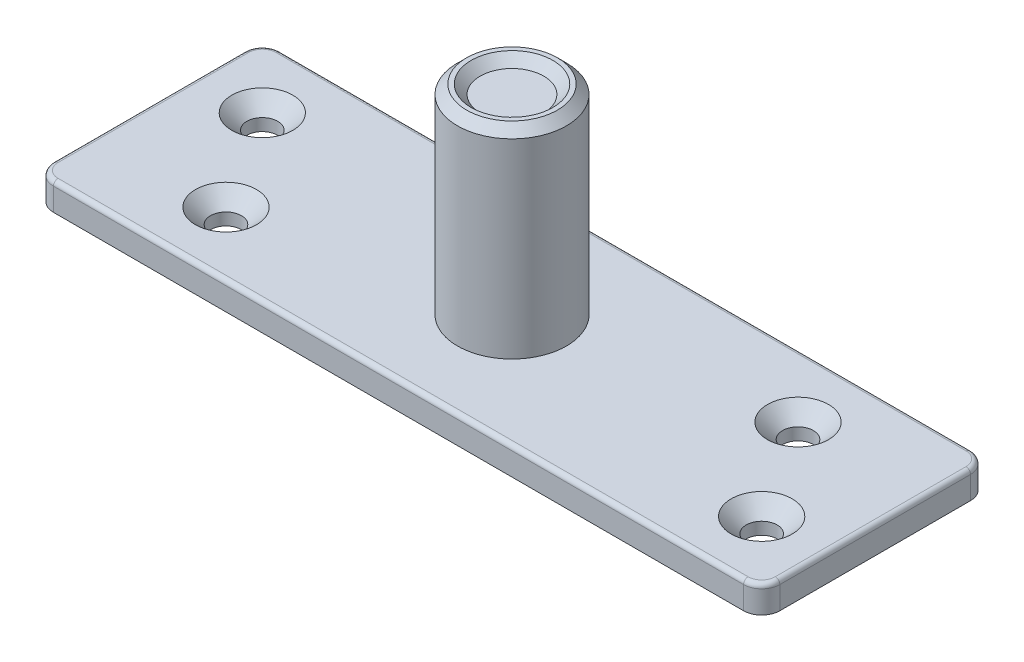
SolidWorks part; units mm, degrees
material "Aço cromo inoxidável"
ref_plane "Plano frontal" through (0, 0, 0) normal (0, 0, 1) x (1, 0, 0)
ref_plane "Plano superior" through (0, 0, 0) normal (0, 1, 0) x (1, 0, 0)
ref_plane "Plano direito" through (0, 0, 0) normal (1, 0, 0) x (0, 0, -1)
other "Caixa delimitadora"
ref_plane "Default Plane" through (-40, -1.5, -12.5) normal (0, 1, 0) x (1, 0, 0)
sketch "Esboço1" plane through (0, 0, 0) normal (0, 1, 0) x (1, 0, 0)
  line L1 (-40, -12.5) -> (40, -12.5)
  line L2 (-40, -12.5) -> (-40, 12.5)
  line L3 (-40, 12.5) -> (40, 12.5)
  line L4 (40, -12.5) -> (40, 12.5)
  line L5 (0, 12.5) -> (0, -12.5) construction
  line L6 (-40, 0) -> (40, 0) construction
  circle A0 centre (0, 0) radius 6
  point P0 (0, 0)
  dimension "D3" = 12
  dimension "D1" = 80
  dimension "D2" = 25
extrude "Ressalto-extrusão1" add sketch "Esboço1" along normal mid plane 3
sketch "Esboço3" plane through (0, -1.5, 0) normal (0, -1, 0) x (1, 0, 0)
  circle A1 centre (0, 0) radius 6 construction
  circle A2 centre (0, 0) radius 6
extrude "Ressalto-extrusão3" add sketch "Esboço3" against normal blind 25 separate body
chamfer "Chanfro1" distance 1 angle 45 2 edges at (0, 23.5, -6) (0, -1.5, -6)
hole_wizard "Escareado para SFHCS M31" positions "Esboço5" profile "Esboço6" countersink size "M3" standard "Ansi Metric" end condition through all
sketch "Esboço5" plane through (0, 1.5, 0) normal (0, 1, 0) x (1, 0, 0)
  line L0 (-40, -12.5) -> (40, -12.5) construction
  line L1 (40, 12.5) -> (-40, 12.5) construction
  line L2 (-40, 12.5) -> (-40, -12.5) construction
  line L3 (40, -12.5) -> (40, 12.5) construction
  point P0 (-33, 5.5)
  point P2 (-26, -5.5)
  point P4 (26, 5.5)
  point P6 (33, -5.5)
  dimension "D1" = 7
  dimension "D2" = 7
  dimension "D3" = 7
  dimension "D4" = 7
  dimension "D5" = 14
  dimension "D6" = 14
sketch "Esboço6" plane through (-33, 1.5, -5.5) normal (1, 0, 0) x (0, 0, 1)
  line L0 (0, 0) -> (0, 3)
  line L1 (0, 3) -> (1.7, 3)
  line L2 (1.7, 3) -> (1.7, 1.66)
  line L3 (1.7, 1.66) -> (3.36, 0)
  line L5 (3.36, 0) -> (0, 0)
  line L6 (-1.7, 1.66) -> (-3.36, 0) construction
  line L11 (0, -6.35) -> (0, 107.95) construction
  dimension "Thru Hole Dia." = 3.4
  dimension "Thru Hole Depth" = 3
  dimension "Near C'Sink Dia." = 6.72
  dimension "Near C'Sink Angle" = 90
fillet "Filete1" radius 2 4 edges at (40, 0, -12.5) (40, 0, 12.5) (-40, 0, -12.5) (-40, 0, 12.5)
fillet "Filete2" radius 0.5 8 edges at (-39.4142, 1.5, 11.9142) (-40, 1.5, 0) (-39.4142, 1.5, -11.9142) (0, 1.5, -12.5) (39.4142, 1.5, -11.9142) (40, 1.5, 0) (39.4142, 1.5, 11.9142) (0, 1.5, 12.5)
delete or keep bodies "Corpo-Excluir/Manter 1" [suppressed] type delete bodies bodies 104
delete or keep bodies "Corpo-Excluir/Manter 2" [suppressed] type delete bodies bodies 105
sketch "Esboço7" plane through (0, 23.5, 0) normal (0, 1, 0) x (1, 0, 0)
  circle A0 centre (0, 0) radius 4.5
  circle A3 centre (0, 0) radius 6 construction
  dimension "D1" = 1.5
extrude "Corte-extrusão1" cut sketch "Esboço7" against normal blind 1
chamfer "Chanfro2" distance 1 angle 45 1 edges at (0, 22.5, 4.5)
equation "\"D4@Esboço5\"=\"D3@Esboço5\""
equation "\"D2@Esboço5\"=\"D3@Esboço5\""
equation "\"D1@Esboço5\"=\"D3@Esboço5\""
equation "\"D5@Esboço5\"=\"D3@Esboço5\"*2"
equation "\"D6@Esboço5\"=\"D5@Esboço5\""
